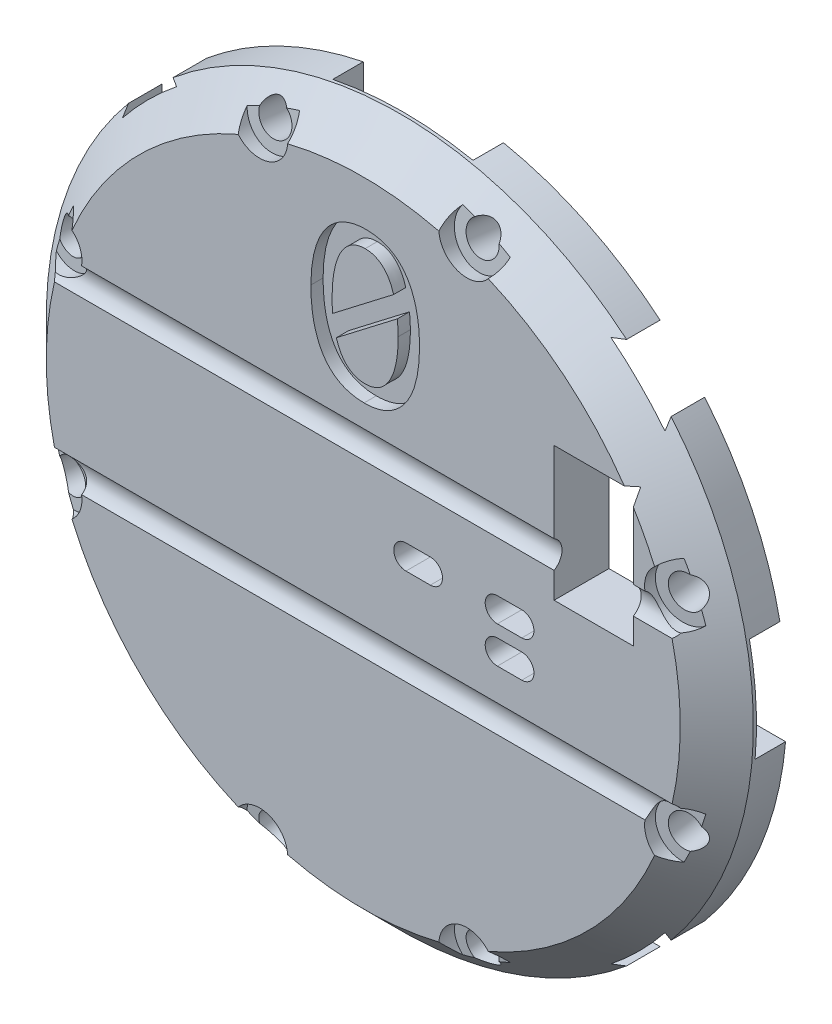
SolidWorks part; units mm, degrees
ref_plane "Front Plane" through (0, 0, 0) normal (0, 0, 1) x (1, 0, 0)
ref_plane "Top Plane" through (0, 0, 0) normal (0, 1, 0) x (1, 0, 0)
ref_plane "Right Plane" through (0, 0, 0) normal (1, 0, 0) x (0, 0, -1)
sketch "Sketch1" plane through (0, 0, 0) normal (0, 0, 1) x (1, 0, 0)
  circle A0 centre (0, 0) radius 29
  dimension "D1" = 58
extrude "Boss-Extrude1" add sketch "Sketch1" along normal blind 5.75
sketch "Sketch3" plane through (0, 0, 0) normal (0, 0, -1) x (-1, 0, 0)
  line L1 (-22.25, -22.25) -> (22.25, -22.25)
  line L2 (-22.25, -22.25) -> (-22.25, 22.25)
  line L3 (-22.25, 22.25) -> (22.25, 22.25)
  line L4 (22.25, -22.25) -> (22.25, 22.25)
  line L5 (-22.25, -22.25) -> (22.25, 22.25) construction
  line L6 (-22.25, 22.25) -> (22.25, -22.25) construction
  point P0 (0, 0)
  dimension "D1" = 44.5
extrude "Cut-Extrude1" cut sketch "Sketch3" against normal blind 3.25
chamfer "Chamfer2" distance 3 angle 45 1 edges at (29, 0, 5.75)
sketch "Sketch9" plane through (0, 0, 0) normal (1, 0, 0) x (0, 0, -1)
  line L0 (-26.5723, 0) -> (15.7273, 0) construction
  line L3 (-5.75, 26) -> (-5.75, -26) construction
  circle A0 centre (-6.4, 7) radius 1.3
  circle A1 centre (-6.4, -7) radius 1.3
  dimension "D1" = 2.6
  dimension "D2" = 14
  dimension "D3" = 0.65
extrude "Cut-Extrude5" cut sketch "Sketch9" against normal through all both and the other way through all
sketch "Sketch10" plane through (0, 0, 0) normal (0, 0, -1) x (-1, 0, 0)
  line L1 (22.0007, 5.75) -> (34.0342, 5.75)
  line L2 (22.0007, 5.75) -> (22.0007, -5.75)
  line L3 (22.0007, -5.75) -> (34.0342, -5.75)
  line L4 (34.0342, 5.75) -> (34.0342, -5.75)
  line L8 (-22.0007, -5.75) -> (-34.0342, -5.75)
  line L9 (-22.0007, -5.75) -> (-22.0007, 5.75)
  line L10 (-22.0007, 5.75) -> (-34.0342, 5.75)
  line L11 (-34.0342, -5.75) -> (-34.0342, 5.75)
  line L12 (-5.75, 22.0007) -> (-5.75, 34.0342)
  line L13 (-5.75, 22.0007) -> (5.75, 22.0007)
  line L14 (5.75, 22.0007) -> (5.75, 34.0342)
  line L15 (-5.75, 34.0342) -> (5.75, 34.0342)
  line L16 (5.75, -22.0007) -> (5.75, -34.0342) [skipped]
  line L17 (5.75, -22.0007) -> (-5.75, -22.0007) [skipped]
  line L18 (-5.75, -22.0007) -> (-5.75, -34.0342) [skipped]
  line L19 (5.75, -34.0342) -> (-5.75, -34.0342) [skipped]
  point P4 (22.0007, 0)
  point P21 (0, 0)
  dimension "D1" = 11.5
  dimension "D2" = 4
extrude "Cut-Extrude6" cut sketch "Sketch10" against normal blind 2.5
sketch "Sketch13" plane through (0, 0, 3.25) normal (0, 0, -1) x (-1, 0, 0)
  line L0 (-22.25, 17.8098) -> (-22.25, -17.8098) construction
  line L1 (-22.15, 14.75) -> (-15.65, 14.75)
  line L2 (-22.15, 14.75) -> (-22.15, 3.75)
  line L3 (-22.15, 3.75) -> (-15.65, 3.75)
  line L4 (-15.65, 14.75) -> (-15.65, 3.75)
  line L5 (17.8098, 22.25) -> (-17.8098, 22.25) construction
  point P8 (0, 0)
  point P23 (0, 0)
  dimension "D1" = 0.1
  dimension "D2" = 7.5
  dimension "D4" = 11
  dimension "D3" = 6.5
extrude "Cut-Extrude9" cut sketch "Sketch13" against normal through all
sketch "Sketch14" plane through (0, 0, 0) normal (0, 0, -1) x (-1, 0, 0)
  line L1 (-35.1198, 0) -> (-19.2322, 0)
  line L2 (-35.1198, 0) -> (-35.1198, -11.6)
  line L3 (-35.1198, -11.6) -> (-19.2322, -11.6)
  line L4 (-19.2322, 0) -> (-19.2322, -11.6)
  dimension "D1" = 11.6
extrude "Cut-Extrude10" cut sketch "Sketch14" against normal up to surface (2.5 mm away) up to face at (25.4811, 0, 2.5)
sketch "Sketch15" plane through (0, 0, 5.75) normal (0, 0, 1) x (1, 0, 0)
  line L0 (0, 0) -> (11.6673, 11.6673) construction
  line L1 (0, 0) -> (36.7921, 0) construction
  circle A0 centre (11.6673, 11.6673) radius 12.5
  circle A1 centre (0, 0) radius 29 construction
  dimension "D2" = 25
  dimension "D1" = 45
ref_axis "Axis1" through (0, 0, -0.2945) along (0, 0, 1)
ref_axis "Axis2" through (0, 31.9, 0) along (0, -1, 0)
ref_plane "Plane1" through (0, 0, 0) normal (0.1219, 0, 0.9925) x (0, -1, 0)
sketch "Sketch23" plane through (0, 0, 2.5) normal (0, 0, -1) x (-1, 0, 0)
  line L0 (-22.25, -2.55) -> (-28.8877, -2.55)
  line L1 (-22.25, -2.55) -> (-22.25, -11.6)
  line L2 (-22.25, -11.6) -> (-26.5789, -11.6)
  line L3 (-22.25, 5.75) -> (-28.4242, 5.75) construction
  arc A0 (-28.8877, -2.55) -> (-26.5789, -11.6) centre (0, 0) ccw
  arc A1 (-28.4242, 5.75) -> (-26.5789, -11.6) centre (0, 0) ccw construction
  dimension "D1" = 8.3
extrude "Boss-Extrude3" add sketch "Sketch23" along normal up to surface (2.5 mm away) up to face at (24.5754, 10.1616, 0)
sketch "Sketch17" plane through (0, 0, 0) normal (0.1219, 0, 0.9925) x (0, -1, 0)
  line L0 (0, 0) -> (0, 33.2124) construction
  line L1 (0, 0.0359) -> (0, -0.7536) construction
  circle A0 centre (-8.5, 24.5) radius 1.35
  circle A1 centre (8.5, 24.5) radius 1.35
  dimension "D1" = 2.7
  dimension "D2" = 17
  dimension "D3" = 24.5
extrude "Cut-Extrude12" cut sketch "Sketch17" along normal through all
sketch "Sketch18" plane through (0, 0, 0) normal (0.1219, 0, 0.9925) x (0, -1, 0)
  circle A0 centre (-8.5, 24.5) radius 2.3
  circle A1 centre (8.5, 24.5) radius 2.3
  dimension "D1" = 4.6
extrude "Cut-Extrude13" cut sketch "Sketch18" against normal blind 12.5 from offset 20
pattern_circular "CirPattern1" count 4 over 360 of "Cut-Extrude12", "Cut-Extrude13"
sketch "Sketch19" plane through (0, 0, 5.75) normal (0, 0, 1) x (1, 0, 0)
  line L0 (3.5, 0.75) -> (5.5, 0.75) construction
  line L1 (3.5, 1.75) -> (5.5, 1.75)
  line L2 (3.5, -0.25) -> (5.5, -0.25)
  line L3 (11, 0.75) -> (13, 0.75) construction
  line L4 (11, 1.75) -> (13, 1.75)
  line L5 (11, -0.25) -> (13, -0.25)
  line L6 (11, -2.25) -> (13, -2.25) construction
  line L7 (11, -1.25) -> (13, -1.25)
  line L8 (11, -3.25) -> (13, -3.25)
  arc A0 (3.5, 1.75) -> (3.5, -0.25) centre (3.5, 0.75) ccw
  arc A1 (5.5, -0.25) -> (5.5, 1.75) centre (5.5, 0.75) ccw
  arc A2 (11, 1.75) -> (11, -0.25) centre (11, 0.75) ccw
  arc A3 (13, -0.25) -> (13, 1.75) centre (13, 0.75) ccw
  arc A4 (11, -1.25) -> (11, -3.25) centre (11, -2.25) ccw
  arc A5 (13, -3.25) -> (13, -1.25) centre (13, -2.25) ccw
  point P2 (4.5, 0.75)
  point P8 (12, 0.75)
  point P16 (12, -2.25)
  dimension "D1" = 1
  dimension "D2" = 3
  dimension "D3" = 7.5
  dimension "D4" = 4.5
  dimension "D5" = 2
  dimension "D6" = 0.75
extrude "Cut-Extrude14" cut sketch "Sketch19" against normal through all
sketch "Sketch21" plane through (0, 0, 3.25) normal (0, 0, -1) x (-1, 0, 0)
  line L61 (-5.5, -0.35) -> (-3.5, -0.35)
  line L62 (-3.5, 1.85) -> (-5.5, 1.85)
  line L63 (-5.5, -0.35) -> (-3.5, -0.35)
  line L64 (-3.5, 1.85) -> (-5.5, 1.85)
  line L69 (-11, 1.85) -> (-13, 1.85)
  line L70 (-13, -0.35) -> (-11, -0.35)
  line L71 (-11, 1.85) -> (-13, 1.85)
  line L72 (-13, -0.35) -> (-11, -0.35)
  line L75 (-5.5, -1.35) -> (-3.5, -1.35)
  line L76 (-3.5, 2.85) -> (-5.5, 2.85)
  line L77 (-11, -1.15) -> (-13, -1.15)
  line L78 (-13, -3.35) -> (-11, -3.35)
  line L79 (-11, -1.15) -> (-13, -1.15)
  line L80 (-13, -3.35) -> (-11, -3.35)
  line L81 (-11, 2.85) -> (-13, 2.85)
  line L84 (-13, -4.35) -> (-11, -4.35)
  line L85 (-13, -1.35) -> (-11, -1.35) construction
  line L86 (-11, -0.15) -> (-13, -0.15) construction
  arc A55 (-5.5, 1.85) -> (-5.5, -0.35) centre (-5.5, 0.75) ccw
  arc A56 (-3.5, -0.35) -> (-3.5, 1.85) centre (-3.5, 0.75) ccw
  arc A57 (-5.5, 1.85) -> (-5.5, -0.35) centre (-5.5, 0.75) ccw
  arc A58 (-3.5, -0.35) -> (-3.5, 1.85) centre (-3.5, 0.75) ccw
  arc A65 (-13, 1.85) -> (-13, -0.35) centre (-13, 0.75) ccw
  arc A66 (-11, -0.35) -> (-11, 1.85) centre (-11, 0.75) ccw
  arc A67 (-13, 1.85) -> (-13, -0.35) centre (-13, 0.75) ccw
  arc A68 (-11, -0.35) -> (-11, 1.85) centre (-11, 0.75) ccw
  arc A73 (-5.5, 2.85) -> (-5.5, -1.35) centre (-5.5, 0.75) ccw
  arc A74 (-3.5, -1.35) -> (-3.5, 2.85) centre (-3.5, 0.75) ccw
  arc A75 (-13, -1.15) -> (-13, -3.35) centre (-13, -2.25) ccw
  arc A76 (-11, -3.35) -> (-11, -1.15) centre (-11, -2.25) ccw
  arc A77 (-13, -1.15) -> (-13, -3.35) centre (-13, -2.25) ccw
  arc A78 (-11, -3.35) -> (-11, -1.15) centre (-11, -2.25) ccw
  arc A80 (-13, 2.85) -> (-14.4697, -0.75) centre (-13, 0.75) ccw
  arc A81 (-11, -4.35) -> (-9.5303, -0.75) centre (-11, -2.25) ccw
  arc A84 (-9.5303, -0.75) -> (-11, 2.85) centre (-11, 0.75) ccw
  arc A85 (-11, -4.35) -> (-11, -0.15) centre (-11, -2.25) ccw construction
  arc A86 (-14.4697, -0.75) -> (-13, -4.35) centre (-13, -2.25) ccw
  arc A87 (-11, -1.35) -> (-11, 2.85) centre (-11, 0.75) ccw construction
  arc A88 (-13, 2.85) -> (-13, -1.35) centre (-13, 0.75) ccw construction
  arc A90 (-13, -0.15) -> (-13, -4.35) centre (-13, -2.25) ccw construction
  dimension "D1" = 0.1
  dimension "D2" = 0.1
  dimension "D3" = 0.1
  dimension "D4" = 1
  dimension "D5" = 1
extrude "Boss-Extrude2" add sketch "Sketch21" along normal blind 2
fillet "Fillet1" radius 1 7 edges at (7.6, 0.75, 3.25) (4.5, 2.85, 3.25) (1.4, 0.75, 3.25) (14.9442, -3.0437, 3.25) (9.0558, -3.0437, 3.25) (4.5, -1.35, 3.25) (12, -4.35, 3.25)
sketch "Sketch24" plane through (0, 0, 5.75) normal (0, 0, 1) x (1, 0, 0)
  line L0 (-5.1692, 10.1499) -> (12.5197, 10.1499) construction
  line L1 (0, 0) -> (0, 40.6298) construction
  text T0 "0" font "Consolas" height in points 46
extrude "Cut-Extrude16" cut sketch "Sketch24" against normal blind 1
sketch "Sketch25" plane through (0, 0, 3.25) normal (0, 0, -1) x (-1, 0, 0)
  line L0 (-22.25, 15.75) -> (-22.25, 14.75)
  line L1 (-22.25, 5.75) -> (-22.25, 18.5994) construction
  line L2 (-22.25, 14.75) -> (-15.65, 14.75)
  line L3 (-15.65, 14.75) -> (-15.65, 3.75)
  line L4 (-15.65, 3.75) -> (-22.25, 3.75)
  line L5 (-22.25, -2.55) -> (-22.25, 5.75) construction
  line L6 (-22.25, 3.75) -> (-22.25, 2.75)
  line L7 (-22.25, 2.75) -> (-14.65, 2.75)
  line L8 (-14.65, 2.75) -> (-14.65, 15.75)
  line L9 (-14.65, 15.75) -> (-22.25, 15.75)
  point P4 (-14.7839, 2.8309)
  point P15 (-14.8475, 15.7193)
  dimension "D1" = 1
  dimension "D2" = 1
  dimension "D3" = 1
extrude "Boss-Extrude4" add sketch "Sketch25" along normal blind 2
chamfer "Chamfer3" distance 0.5 angle 45 3 edges at (18.45, 15.75, 1.25) (18.45, 2.75, 1.25) (14.65, 9.25, 1.25)
